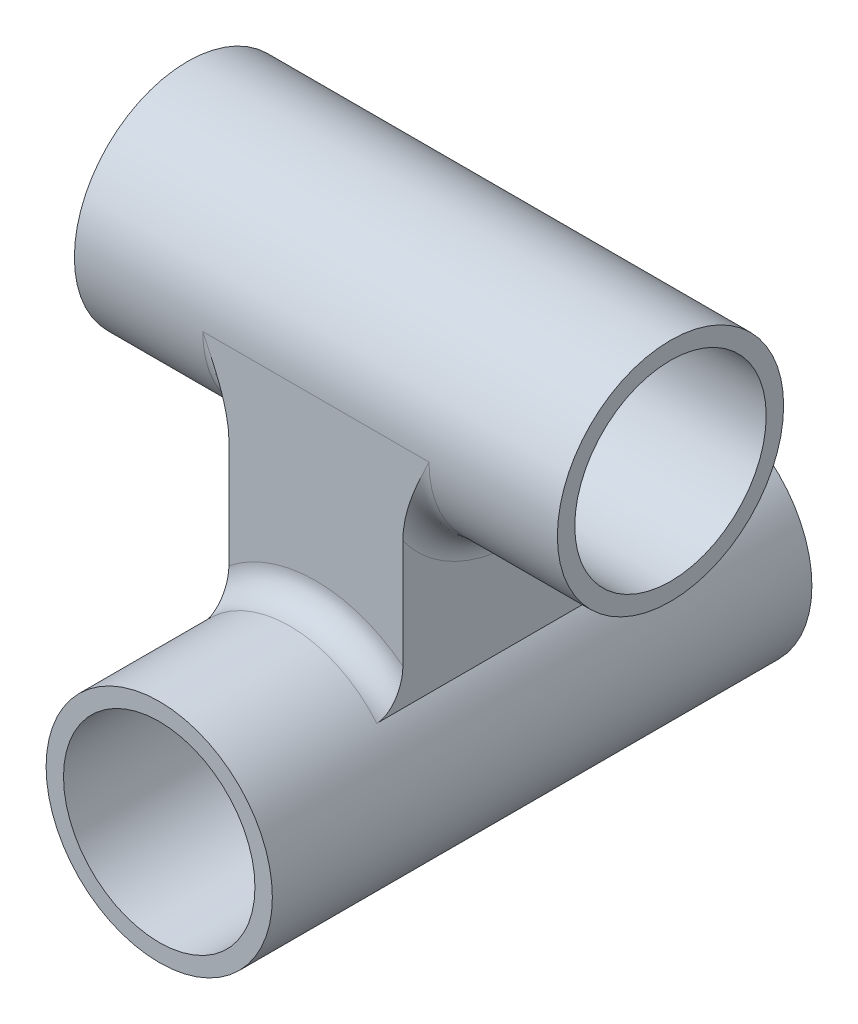
SolidWorks part; units mm, degrees
ref_plane "前视基准面" through (0, 0, 0) normal (0, 0, 1) x (1, 0, 0)
ref_plane "上视基准面" through (0, 0, 0) normal (0, 1, 0) x (1, 0, 0)
ref_plane "右视基准面" through (0, 0, 0) normal (1, 0, 0) x (0, 0, -1)
sketch "草图1" plane through (0, 0, 0) normal (0, 0, 1) x (1, 0, 0)
  circle A0 centre (0, 0) radius 11
  circle A1 centre (0, 0) radius 13
  dimension "D1" = 22
  dimension "D2" = 26
extrude "凸台-拉伸1" add sketch "草图1" along normal mid plane 62
sketch "草图2" plane through (0, 0, 31) normal (0, 0, 1) x (1, 0, 0)
  circle A0 centre (0, 0) radius 8
  circle A1 centre (0, 0) radius 15.3036
  dimension "D1" = 16
extrude "切除-拉伸1" [suppressed] cut sketch "草图2" against normal blind 1
sketch "草图3" plane through (0, 0, -31) normal (0, 0, -1) x (-1, 0, 0)
  circle A0 centre (0, 0) radius 8
  circle A1 centre (0, 0) radius 12.8563
  dimension "D1" = 16
extrude "切除-拉伸2" [suppressed] cut sketch "草图3" against normal blind 1
sketch "草图4" plane through (0, 0, 0) normal (0, 0, 1) x (1, 0, 0)
  line L2 (-10, 8.3066) -> (-10, 34.3066)
  line L3 (-10, 34.3066) -> (10, 34.3066)
  line L4 (10, 8.3066) -> (10, 34.3066)
  arc A0 (10, 8.3066) -> (-10, 8.3066) centre (0, 0) ccw
  dimension "D2" = 26
  dimension "D1" = 10
  dimension "D3" = 10
  dimension "D4" = 26
extrude "凸台-拉伸2" add sketch "草图4" along normal mid plane 26
sketch "草图6" plane through (0, 0, 0) normal (1, 0, 0) x (0, 0, -1)
  line L0 (-13, 34.3066) -> (13, 34.3066) construction
  circle A0 centre (0, 34.3066) radius 13
extrude "凸台-拉伸3" add sketch "草图6" along normal mid plane 55.5
sketch "草图7" plane through (27.75, 0, 0) normal (1, 0, 0) x (0, 0, -1)
  circle A0 centre (0, 34.3066) radius 11
  dimension "D1" = 22
extrude "切除-拉伸3" cut sketch "草图7" against normal mid plane 180
sketch "草图8" plane through (27.75, 0, 0) normal (1, 0, 0) x (0, 0, -1)
  circle A0 centre (0, 34.3066) radius 8
  circle A1 centre (0, 34.3066) radius 14.0412
  dimension "D1" = 16
extrude "切除-拉伸4" [suppressed] cut sketch "草图8" against normal blind 1
sketch "草图9" plane through (-27.75, 0, 0) normal (-1, 0, 0) x (0, 0, 1)
  circle A0 centre (0, 34.3066) radius 8
  circle A1 centre (0, 34.3066) radius 13.5239
  dimension "D1" = 16
extrude "切除-拉伸5" [suppressed] cut sketch "草图9" against normal blind 1
fillet "圆角1" radius 3 4 edges at (0, 13, -13) (0, 13, 13) (10, 21.3066, 0) (-10, 21.3066, 0)
